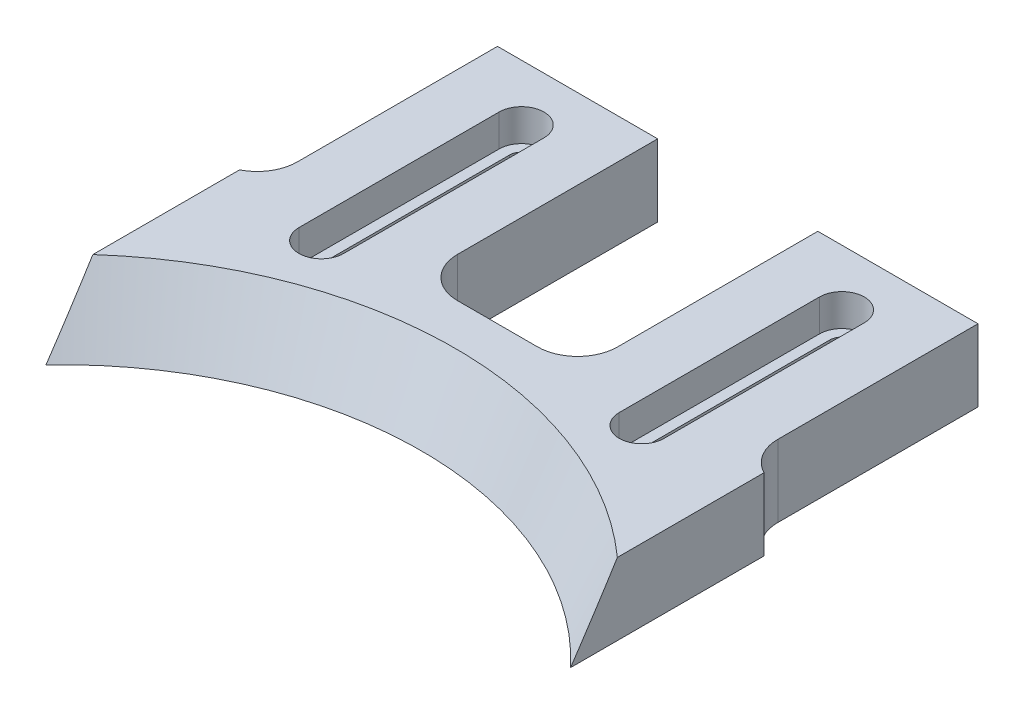
SolidWorks part; units mm, degrees
material "POM Acetal Copolymer"
ref_plane "Front Plane" through (0, 0, 0) normal (0, 0, 1) x (1, 0, 0)
ref_plane "Top Plane" through (0, 0, 0) normal (0, 1, 0) x (1, 0, 0)
ref_plane "Right Plane" through (0, 0, 0) normal (1, 0, 0) x (0, 0, -1)
sketch "Sketch1" plane through (0, 0, 0) normal (0, 1, 0) x (1, 0, 0)
  line L0 (0, 0) -> (0, 60)
  line L1 (0, 60) -> (75.5, 60)
  line L2 (75.5, 60) -> (75.5, 0)
  arc A0 (0, 0) -> (75.5, 0) centre (37.75, -24.4936) cw
  dimension "D5" = 45
  dimension "D1" = 60
  dimension "D3" = 75.5
extrude "Boss-Extrude1" add sketch "Sketch1" along normal blind 9
sketch "Sketch4" plane through (0, 9, 0) normal (0, 1, 0) x (1, 0, 0)
  line L0 (17.75, 53) -> (17.75, 28) construction
  line L1 (19.25, 53) -> (19.25, 28)
  line L2 (16.25, 53) -> (16.25, 28)
  line L3 (57.75, 53) -> (57.75, 28) construction
  line L4 (59.25, 53) -> (59.25, 28)
  line L5 (56.25, 53) -> (56.25, 28)
  line L6 (75.5, 60) -> (0, 60) construction
  line L9 (75.5, 60) -> (0, 60) construction
  arc A0 (19.25, 53) -> (16.25, 53) centre (17.75, 53) ccw
  arc A1 (16.25, 28) -> (19.25, 28) centre (17.75, 28) ccw
  arc A2 (59.25, 53) -> (56.25, 53) centre (57.75, 53) ccw
  arc A3 (56.25, 28) -> (59.25, 28) centre (57.75, 28) ccw
  point P2 (17.75, 40.5)
  point P7 (57.75, 40.5)
  point P14 (37.75, 60)
  dimension "D1" = 3
  dimension "D2" = 3
  dimension "D3" = 40
  dimension "D4" = 20
  dimension "D5" = 25
  dimension "D6" = 7
extrude "Cut-Extrude2" cut sketch "Sketch4" against normal up to next
sketch "Sketch5" plane through (0, 9, 0) normal (0, 1, 0) x (1, 0, 0)
  line L0 (75.5, 60) -> (0, 60) construction
  line L1 (27.75, 60) -> (47.75, 60)
  line L2 (27.75, 60) -> (27.75, 30)
  line L3 (27.75, 30) -> (47.75, 30)
  line L4 (47.75, 60) -> (47.75, 30)
  line L7 (67.75, 60) -> (75.5, 60)
  line L8 (0, 60) -> (7.75, 60)
  line L9 (0, 60) -> (0, 30)
  line L10 (0, 30) -> (7.75, 30)
  line L11 (7.75, 60) -> (7.75, 30)
  line L12 (67.75, 60) -> (67.75, 30)
  line L13 (67.75, 30) -> (75.5, 30)
  line L14 (75.5, 60) -> (75.5, 30)
  arc A0 (19.25, 53) -> (16.25, 53) centre (17.75, 53) ccw construction
  arc A1 (59.25, 53) -> (56.25, 53) centre (57.75, 53) ccw construction
  point P6 (17.75, 54.5)
  point P21 (57.75, 54.5)
  dimension "D1" = 20
  dimension "D2" = 20
  dimension "D3" = 30
  dimension "D4" = 10
  dimension "D5" = 10
extrude "Cut-Extrude3" cut sketch "Sketch5" against normal blind 10
fillet "Fillet1" radius 5 4 edges at (67.75, 4.5, -30) (47.75, 4.5, -30) (27.75, 4.5, -30) (7.75, 4.5, -30)
sketch "Sketch6" plane through (0, 9, 0) normal (0, 1, 0) x (1, 0, 0)
  line L0 (17.75, 53) -> (17.75, 28) construction
  line L1 (20.55, 53) -> (20.55, 28)
  line L2 (14.95, 53) -> (14.95, 28)
  line L3 (57.75, 53) -> (57.75, 28) construction
  line L4 (60.55, 53) -> (60.55, 28)
  line L5 (54.95, 53) -> (54.95, 28)
  arc A0 (20.55, 53) -> (14.95, 53) centre (17.75, 53) ccw
  arc A1 (14.95, 28) -> (20.55, 28) centre (17.75, 28) ccw
  arc A2 (60.55, 53) -> (54.95, 53) centre (57.75, 53) ccw
  arc A3 (54.95, 28) -> (60.55, 28) centre (57.75, 28) ccw
  point P4 (17.75, 40.5)
  point P9 (57.75, 40.5)
  dimension "D1" = 5.6
  dimension "D2" = 5.6
extrude "Cut-Extrude4" cut sketch "Sketch6" against normal blind 4
chamfer "Chamfer1" distance 9 angle 25 1 edges at (37.75, 9, -20.5064) first distance on face at (37.75, 4.5, -10.2532)
sketch "Sketch7" plane through (0, 9, 0) normal (0, 1, 0) x (1, 0, 0)
  line L1 (0, 0) -> (5, 0)
  line L2 (0, 0) -> (0, 33.0851)
  line L3 (0, 33.0851) -> (5, 33.0851)
  line L4 (5, 0) -> (5, 33.0851)
  line L5 (75.5, 0) -> (70.5, 0)
  line L6 (75.5, 0) -> (75.5, 33.7453)
  line L7 (75.5, 33.7453) -> (70.5, 33.7453)
  line L8 (70.5, 0) -> (70.5, 33.7453)
  dimension "D1" = 5
extrude "Cut-Extrude5" cut sketch "Sketch7" against normal up to next
